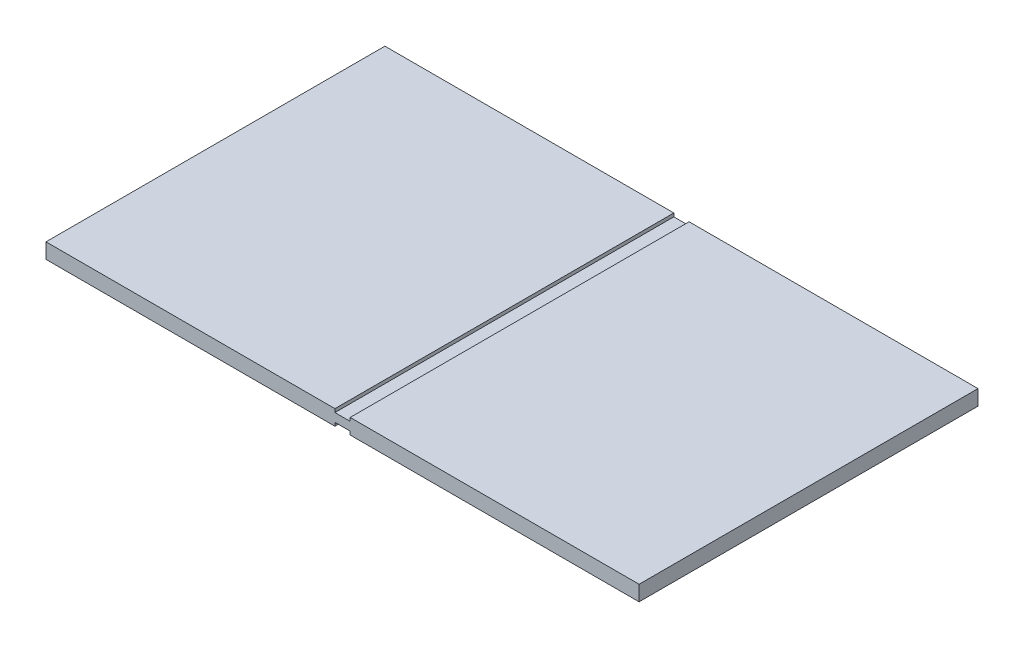
SolidWorks part; units mm, degrees
ref_plane "Front" through (0, 0, 0) normal (0, 0, 1) x (1, 0, 0)
ref_plane "Top" through (0, 0, 0) normal (0, 1, 0) x (1, 0, 0)
ref_plane "Right" through (0, 0, 0) normal (1, 0, 0) x (0, 0, -1)
sketch "Sketch1" plane through (0, 0, 0) normal (0, 1, 0) x (1, 0, 0)
  line L1 (-350, -200) -> (350, -200)
  line L2 (-350, -200) -> (-350, 200)
  line L3 (-350, 200) -> (350, 200)
  line L4 (350, -200) -> (350, 200)
  line L5 (-350, -200) -> (350, 200) construction
  line L6 (-350, 200) -> (350, -200) construction
  point P0 (0, 0)
  dimension "D1" = 700
  dimension "D2" = 400
extrude "Boss-Extrude1" add sketch "Sketch1" along normal blind 18
sketch "Sketch2" plane through (0, 18, 0) normal (0, 1, 0) x (1, 0, 0)
  line L0 (350, 200) -> (-350, 200) construction
  line L1 (9, -200) -> (-9, -200)
  line L2 (9, -200) -> (9, 200)
  line L3 (9, 200) -> (-9, 200)
  line L4 (-9, -200) -> (-9, 200)
  line L5 (9, -200) -> (-9, 200) construction
  line L6 (9, 200) -> (-9, -200) construction
  point P0 (0, 0)
  dimension "D1" = 18
extrude "Cut-Extrude1" cut sketch "Sketch2" against normal blind 4
sketch "Sketch3" plane through (0, 0, 0) normal (0, -1, 0) x (-1, 0, 0)
  line L0 (350, -200) -> (-350, -200) construction
  line L1 (9, 200) -> (-9, 200)
  line L2 (9, 200) -> (9, -200)
  line L3 (9, -200) -> (-9, -200)
  line L4 (-9, 200) -> (-9, -200)
  line L5 (9, 200) -> (-9, -200) construction
  line L6 (9, -200) -> (-9, 200) construction
  point P0 (0, 0)
  dimension "D1" = 18
extrude "Cut-Extrude2" cut sketch "Sketch3" against normal blind 4
